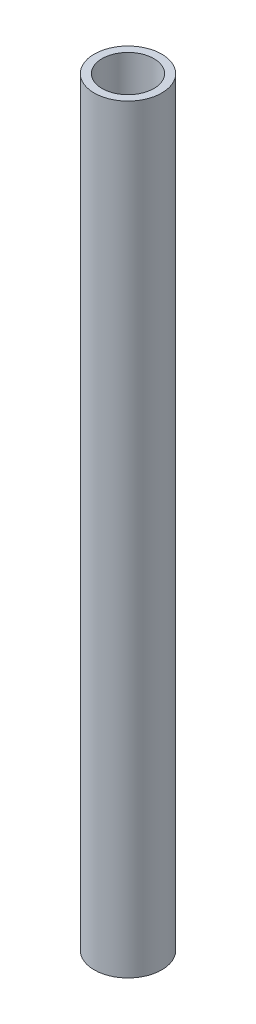
SolidWorks part; units mm, degrees
material "AISI 4130 Steel, annealed at 865C"
ref_plane "X-Y Datum" through (0, 0, 0) normal (0, 0, 1) x (1, 0, 0)
ref_plane "X-Z Datum" through (0, 0, 0) normal (0, 1, 0) x (1, 0, 0)
ref_plane "Y-Z Datum" through (0, 0, 0) normal (1, 0, 0) x (0, 0, -1)
sketch "Sketch1" plane through (0, 0, 0) normal (0, 1, 0) x (1, 0, 0)
  circle A0 centre (0, 0) radius 6.35
  circle A1 centre (0, 0) radius 4.8768
  dimension "D1" = 12.7
  dimension "D2" = 1.4732
extrude "Boss-Extrude1" add sketch "Sketch1" along normal blind 142.875
